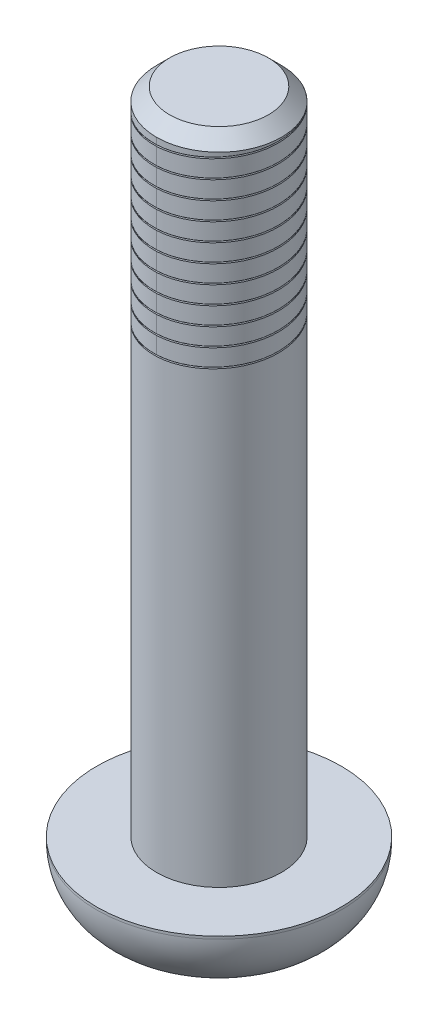
SolidWorks part; units mm, degrees
ref_plane "Front Plane" through (0, 0, 0) normal (0, 0, 1) x (1, 0, 0)
ref_plane "Top Plane" through (0, 0, 0) normal (0, 1, 0) x (1, 0, 0)
ref_plane "Right Plane" through (0, 0, 0) normal (1, 0, 0) x (0, 0, -1)
sketch "Sketch1" plane through (0, 0, 0) normal (0, 1, 0) x (1, 0, 0)
  line L1 (5.4271, 0) -> (2.7135, 4.7) construction
  line L2 (2.7135, 4.7) -> (-2.7135, 4.7) construction
  line L3 (-2.7135, 4.7) -> (-5.4271, 0) construction
  line L4 (-5.4271, 0) -> (-2.7135, -4.7) construction
  line L5 (-2.7135, -4.7) -> (2.7135, -4.7) construction
  line L6 (2.7135, -4.7) -> (5.4271, 0) construction
  circle A0 centre (0, 0) radius 4.7
  dimension "D1" = 9.4
extrude "Boss-Extrude1" add sketch "Sketch1" along normal blind 27.6
sketch "Sketch2" plane through (0, 27.6, 0) normal (0, 1, 0) x (1, 0, 0)
  circle A0 centre (0, 0) radius 2.4
  dimension "D1" = 4.8
extrude "Cut-Extrude1" cut sketch "Sketch2" against normal blind 25 flip side to cut
ref_axis "Axis1" through (0, 2.6, 0) along (0, 1, 0)
chamfer "Chamfer1" distance 0.5 angle 45 1 edges at (0, 27.6, 2.4)
sketch "Sketch5" plane through (0, 27.6, 0) normal (0, 1, 0) x (1, 0, 0)
  circle A0 centre (0, 0) radius 2.5
  dimension "D1" = 5
curve "Helix/Spiral1" pitch 0.7 height 8 radius 2.5 centre (0, 27.6, 0) axis (0, -1, 0) start towards (0, 0, 1)
ref_plane "Plane1" through (0, 27.6, 2.5) normal (-0.999, -0.0445, 0) x (0, 0, 1)
sketch "Sketch7" plane through (0, 27.6, 2.5) normal (-0.999, -0.0445, 0) x (0, 0, 1)
  line L0 (-0.081, -0.0303) -> (0.549, 0.2747)
  line L1 (0.549, 0.2747) -> (0.549, -0.4253)
  line L2 (0.549, -0.4253) -> (-0.081, -0.1203)
  arc A0 (-0.081, -0.0303) -> (-0.081, -0.1203) centre (-0.0592, -0.0753) ccw
  dimension "D2" = 0.05
  dimension "D1" = 0.7
sketch "Sketch8" plane through (0, 0, 0) normal (0, -1, 0) x (1, 0, 0)
  line L1 (1.6743, 0) -> (0.8372, 1.45)
  line L2 (0.8372, 1.45) -> (-0.8372, 1.45)
  line L3 (-0.8372, 1.45) -> (-1.6743, 0)
  line L4 (-1.6743, 0) -> (-0.8372, -1.45)
  line L5 (-0.8372, -1.45) -> (0.8372, -1.45)
  line L6 (0.8372, -1.45) -> (1.6743, 0)
  circle A0 centre (0, 0) radius 1.45 construction
  dimension "D1" = 2.9
extrude "Cut-Extrude2" cut sketch "Sketch8" against normal blind 1.5
sweep "Cut-Sweep1" cut profiles "Sketch7" path "Helix/Spiral1" align with end faces yes
fillet "Fillet1" radius 2.5 1 edges at (0, 0, 4.7)
